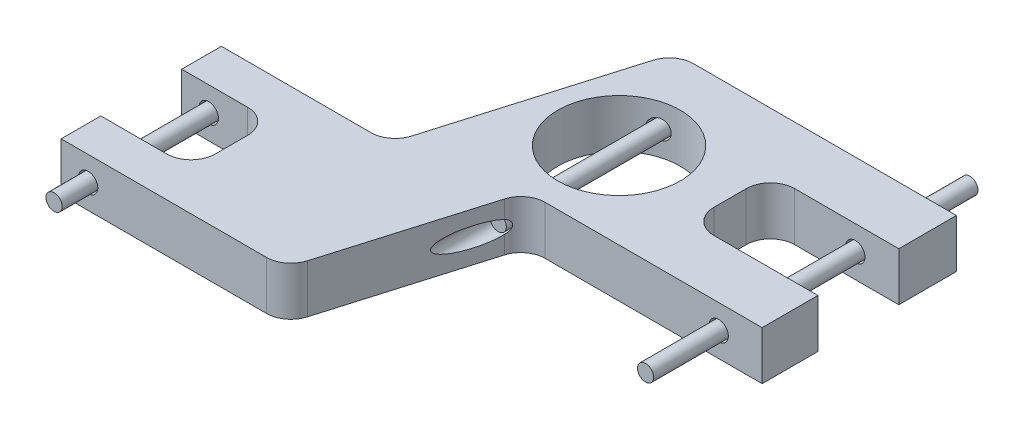
SolidWorks part; units mm, degrees
note: The reader was unsure of these and kept them because the rebuilt part matched: shared geometry of "Sketch24<3>", "Sketch24<4>".
ref_plane "Front Plane" through (0, 0, 0) normal (0, 0, 1) x (1, 0, 0)
ref_plane "Top Plane" through (0, 0, 0) normal (0, 1, 0) x (1, 0, 0)
ref_plane "Right Plane" through (0, 0, 0) normal (1, 0, 0) x (0, 0, -1)
sketch "Sketch21" plane through (0, 0, 0) normal (0, 1, 0) x (1, 0, 0)
  line L0 (-68.3493, -4.0266) -> (-58.0049, -4.0266)
  line L1 (-54.1949, -7.8366) -> (-54.1949, -12.9166)
  line L2 (-58.0049, -16.7266) -> (-68.3493, -16.7266)
  line L3 (-68.3493, -16.7266) -> (-68.3493, -22.9496)
  line L4 (12.3038, 6.3892) -> (12.3038, 15.134)
  line L5 (-68.3493, -22.9496) -> (-36.1125, -22.9496)
  line L6 (-68.3493, -4.0266) -> (-68.3493, 2.1964)
  line L7 (12.3038, 27.834) -> (-4.0242, 27.834)
  line L8 (52.8639, 77.8829) -> (52.8639, -77.8829) construction
  line L9 (12.3038, 6.3892) -> (-21.7488, 6.3892)
  line L10 (-7.8342, 24.024) -> (-7.8342, 18.944)
  line L11 (-4.0242, 15.134) -> (12.3038, 15.134)
  line L12 (12.3038, 27.834) -> (12.3038, 36.8724)
  line L14 (-41.2327, 4.9267) -> (-32.5996, 34.1421)
  line L15 (-28.9458, 36.8724) -> (12.3038, 36.8724)
  line L16 (-25.4027, 3.6589) -> (-32.4586, -20.2193)
  line L17 (-68.3493, 2.1964) -> (-44.8866, 2.1964)
  circle A0 centre (-23.6637, 19.9075) radius 9.619
  circle A1 centre (-23.6637, 19.9075) radius 17.239 construction
  arc A2 (-32.5996, 34.1421) -> (-28.9458, 36.8724) centre (-28.9458, 33.0624) cw
  arc A3 (-44.8866, 2.1964) -> (-41.2327, 4.9267) centre (-44.8866, 6.0064) ccw
  arc A4 (-32.4586, -20.2193) -> (-36.1125, -22.9496) centre (-36.1125, -19.1396) cw
  arc A5 (-25.4027, 3.6589) -> (-21.7488, 6.3892) centre (-21.7488, 2.5792) cw
  arc A6 (-58.0049, -4.0266) -> (-54.1949, -7.8366) centre (-58.0049, -7.8366) cw
  arc A7 (-54.1949, -12.9166) -> (-58.0049, -16.7266) centre (-58.0049, -12.9166) cw
  arc A8 (-4.0242, 27.834) -> (-7.8342, 24.024) centre (-4.0242, 24.024) ccw
  arc A9 (-7.8342, 18.944) -> (-4.0242, 15.134) centre (-4.0242, 18.944) ccw
  point P35 (-54.1949, -4.0266)
  point P38 (-54.1949, -16.7266)
  point P39 (-7.8342, 27.834)
  point P42 (-7.8342, 15.134)
  dimension "D7" = 7.62
  dimension "D5" = 3.81
  dimension "D1" = 3.81
  dimension "D2" = 12.7
  dimension "D3" = 12.7
  dimension "D4" = 30.4831
  dimension "D8" = 6.223
extrude "Extrude1" add sketch "Sketch21" along normal mid plane 7.62
sketch "Sketch22" plane through (0, 0, -36.8724) normal (0, 0, -1) x (-1, 0, 0)
  circle A0 centre (-5.4792, 0) radius 1.524
  circle A1 centre (64.1168, 0) radius 1.524
  circle A2 centre (26.5284, 0) radius 1.524
  dimension "D1" = 69.596
  dimension "D2" = 3.048
extrude "Cut-Extrude1" cut sketch "Sketch22" against normal mid plane 183.515
sketch "Sketch24" plane through (0, 0, 0) normal (0, 0, 1) x (1, 0, 0)
  circle A0 centre (-26.5284, 0) radius 1.27
  circle A1 centre (-64.1168, 0) radius 1.27
  circle A2 centre (5.4792, 0) radius 1.27
  dimension "D1" = 2.54
extrude "Extrude2" add sketch "Sketch24" against normal blind 34.29 from offset 3.81 separate body contours A0
extrude "Extrude3" add sketch "Sketch24<3>" along normal blind 28.288 separate body contours A1
sketch "Sketch24<3>" plane through (0, 0, 0) normal (0, 0, 1) x (1, 0, 0) same geometry as "Sketch24"
extrude "Extrude4" add sketch "Sketch24<4>" against normal blind 50.894 from offset 5.08 separate body contours A2
sketch "Sketch24<4>" plane through (0, 0, 0) normal (0, 0, 1) x (1, 0, 0) same geometry as "Sketch24"
